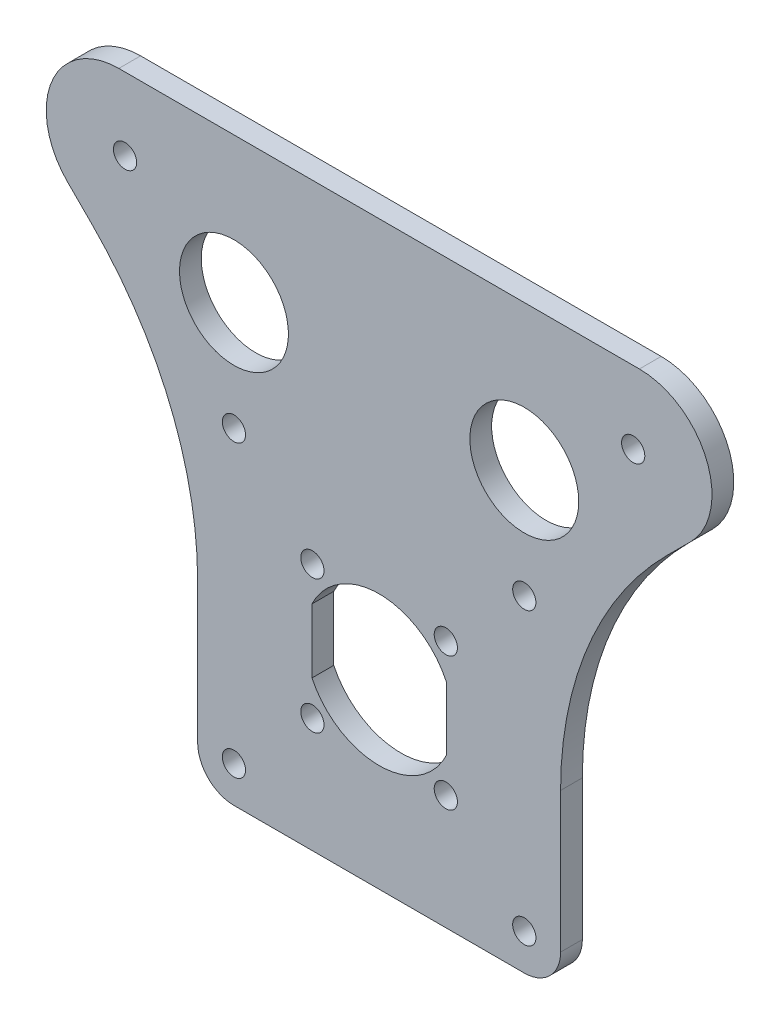
SolidWorks part; units mm, degrees
ref_plane "正面" through (0, 0, 0) normal (0, 0, 1) x (1, 0, 0)
ref_plane "平面" through (0, 0, 0) normal (0, 1, 0) x (1, 0, 0)
ref_plane "右側面" through (0, 0, 0) normal (1, 0, 0) x (0, 0, -1)
sketch "ｽｹｯﾁ1" plane through (0, 0, 0) normal (0, 0, 1) x (1, 0, 0)
  line L1 (-20, 20) -> (20, 20) construction
  line L2 (-20, 20) -> (-20, -20) construction
  line L3 (-20, -20) -> (20, -20) construction
  line L4 (20, 20) -> (20, -20) construction
  line L5 (-20, 20) -> (20, -20) construction
  line L6 (-20, -20) -> (20, 20) construction
  line L7 (-9.1924, 9.1924) -> (9.1924, 9.1924) construction
  line L8 (-9.1924, 9.1924) -> (-9.1924, -9.1924) construction
  line L9 (-9.1924, -9.1924) -> (9.1924, -9.1924) construction
  line L10 (9.1924, 9.1924) -> (9.1924, -9.1924) construction
  line L11 (-9.1924, 9.1924) -> (9.1924, -9.1924) construction
  line L12 (-9.1924, -9.1924) -> (9.1924, 9.1924) construction
  line L13 (-25, 25) -> (25, 25)
  line L14 (-25, 25) -> (-25, -25)
  line L15 (-25, -25) -> (25, -25)
  line L16 (25, 25) -> (25, -25)
  line L17 (-25, 25) -> (25, -25) construction
  line L18 (-25, -25) -> (25, 25) construction
  circle A0 centre (-20, 20) radius 1.6
  circle A1 centre (-9.1924, 9.1924) radius 1.6
  circle A2 centre (9.1924, 9.1924) radius 1.6
  circle A3 centre (20, 20) radius 1.6
  circle A4 centre (9.1924, -9.1924) radius 1.6
  circle A5 centre (20, -20) radius 1.6
  circle A6 centre (-9.1924, -9.1924) radius 1.6
  circle A7 centre (-20, -20) radius 1.6
  point P0 (0, 0)
  point P5 (0, 0)
  point P10 (0, 0)
  dimension "D3" = 4
  dimension "D4" = 3.2
  dimension "D1" = 40
  dimension "D2" = 13
  dimension "D5" = 50
extrude "ﾎﾞｽ - 押し出し1" add sketch "ｽｹｯﾁ1" along normal blind 3
fillet "ﾌｨﾚｯﾄ1" radius 5 4 edges at (25, -25, 1.5) (-25, -25, 1.5) (-25, 25, 1.5) (25, 25, 1.5)
sketch "ｽｹｯﾁ2" plane through (0, 0, 3) normal (0, 0, 1) x (1, 0, 0)
  line L0 (-9.25, 4.4159) -> (-9.25, -4.4159)
  line L2 (9.25, -4.4159) -> (9.25, 4.4159)
  arc A0 (-9.25, -4.4159) -> (9.25, -4.4159) centre (0, 0) ccw
  arc A1 (9.25, 4.4159) -> (-9.25, 4.4159) centre (0, 0) ccw
  dimension "D1" = 18.5
  dimension "D2" = 20.5
extrude "ｶｯﾄ - 押し出し1" cut sketch "ｽｹｯﾁ2" against normal through all
sketch "ｽｹｯﾁ3" plane through (0, 0, 3) normal (0, 0, 1) x (1, 0, 0)
  line L0 (-25, 20) -> (-42.9289, 37.9289)
  line L1 (-35.8579, 55) -> (35.8579, 55)
  line L2 (42.9289, 37.9289) -> (25, 20)
  line L3 (25, -20) -> (25, 20) construction
  line L4 (-25, 20) -> (-25, -20) construction
  line L5 (20, 25) -> (-20, 25) construction
  line L10 (-20, -25) -> (20, -25)
  line L11 (25, -20) -> (25, 20)
  line L12 (20, 25) -> (-20, 25)
  line L13 (-25, 20) -> (-25, -20)
  line L16 (20, 25) -> (-20, 25)
  arc A0 (35.8579, 55) -> (42.9289, 37.9289) centre (35.8579, 45) cw
  arc A1 (-42.9289, 37.9289) -> (-35.8579, 55) centre (-35.8579, 45) cw
  arc A6 (20, -25) -> (25, -20) centre (20, -20) ccw
  arc A7 (25, 20) -> (20, 25) centre (20, 20) ccw
  arc A8 (-20, 25) -> (-25, 20) centre (-20, 20) ccw
  arc A9 (-25, -20) -> (-20, -25) centre (-20, -20) ccw
  arc A11 (25, 20) -> (20, 25) centre (20, 20) ccw
  arc A12 (-20, 25) -> (-25, 20) centre (-20, 20) ccw
  dimension "D4" = 10
  dimension "D1" = 135
  dimension "D2" = 135
  dimension "D3" = 30
  dimension "D5" = 0
extrude "ﾎﾞｽ - 押し出し2" add sketch "ｽｹｯﾁ3" against normal through all
fillet "ﾌｨﾚｯﾄ2" radius 50 2 edges at (-25, 20, 1.5) (25, 20, 1.5)
sketch "ｽｹｯﾁ4" plane through (0, 0, 3) normal (0, 0, 1) x (1, 0, 0)
  line L0 (-50, 45) -> (50, 45) construction
  line L1 (-42.9289, 37.9289) -> (-39.6447, 34.6447) construction
  line L2 (39.6447, 34.6447) -> (42.9289, 37.9289) construction
  line L3 (35.8579, 55) -> (-35.8579, 55) construction
  line L4 (0, 0) -> (0, 45) construction
  circle A0 centre (-35, 45) radius 1.6
  circle A1 centre (35, 45) radius 1.6
  dimension "D2" = 35
  dimension "D3" = 3.2
  dimension "D1" = 10
extrude "ｶｯﾄ - 押し出し2" cut sketch "ｽｹｯﾁ4" against normal through all
sketch "ｽｹｯﾁ5" plane through (0, 0, 3) normal (0, 0, 1) x (1, 0, 0)
  line L0 (0, 0) -> (0, 55) construction
  line L1 (35.8579, 55) -> (-35.8579, 55) construction
  circle A0 centre (20, 35) radius 7.5
  circle A1 centre (-20, 35) radius 7.5
  point P7 (18.5326, 33.5737)
  point P10 (0, 31.6611)
  dimension "D1" = 15
  dimension "D2" = 20
  dimension "D3" = 20
extrude "ｶｯﾄ - 押し出し3" cut sketch "ｽｹｯﾁ5" against normal through all
